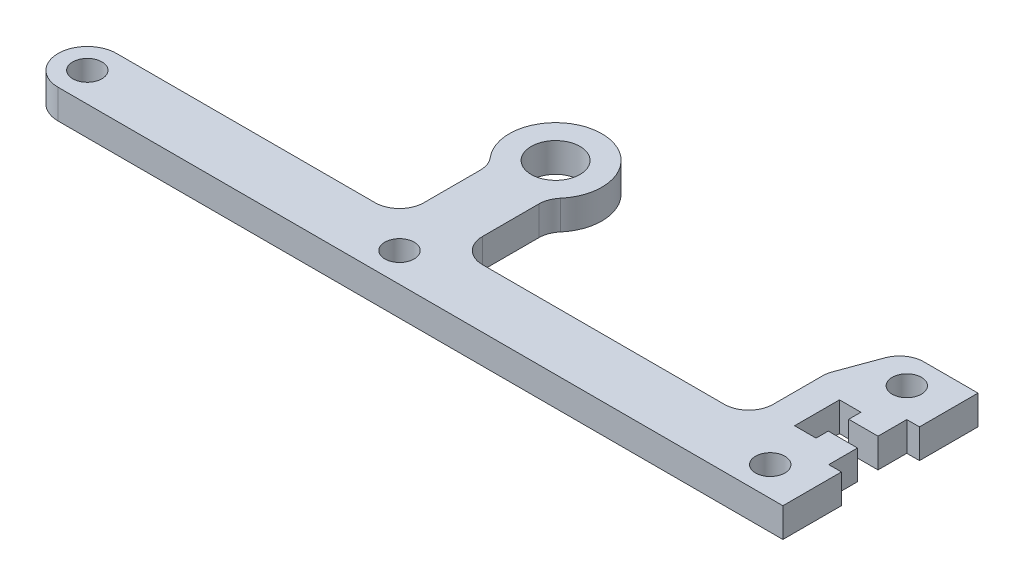
SolidWorks part; units mm, degrees
ref_plane "Front Plane" through (0, 0, 0) normal (0, 0, 1) x (1, 0, 0)
ref_plane "Top Plane" through (0, 0, 0) normal (0, 1, 0) x (1, 0, 0)
ref_plane "Right Plane" through (0, 0, 0) normal (1, 0, 0) x (0, 0, -1)
sketch "Sketch1" plane through (0, 0, 0) normal (0, 1, 0) x (1, 0, 0)
  line L0 (0, 13.2826) -> (0, -17.1967) construction
  line L5 (-2.5, 0) -> (-4.75, 0) construction
  line L6 (-3, -13) -> (3, -13)
  line L7 (-3, -13) -> (-3, -3.6827)
  line L8 (-3, -3.6827) -> (3, -3.6827)
  line L9 (3, -13) -> (3, -3.6827)
  line L10 (-3, -13) -> (3, -3.6827) construction
  line L11 (-3, -3.6827) -> (3, -13) construction
  line L12 (-19.9844, -5) -> (18.0407, -5) construction
  line L13 (-35, -19) -> (35, -19)
  line L14 (-35, -19) -> (-35, -13)
  line L15 (-35, -13) -> (35, -13)
  line L16 (35, -19) -> (35, -13)
  line L17 (-35, -19) -> (35, -13) construction
  line L18 (-35, -13) -> (35, -19) construction
  line L19 (-20.8891, -8) -> (20.8891, -8) construction
  line L20 (-35, -16) -> (35, -16) construction
  line L22 (35, -19) -> (41, -19)
  line L23 (35, -19) -> (35, 1)
  line L24 (35, 1) -> (41, 1)
  line L25 (41, -19) -> (41, 1)
  line L26 (38, 1) -> (38, -19) construction
  line L27 (35, -9) -> (41, -9) construction
  line L28 (32.8, -5) -> (32.8, -13)
  line L29 (38, -7.95) -> (41, -7.95)
  line L30 (38, -7.95) -> (38, -10.05)
  line L31 (38, -10.05) -> (41, -10.05)
  line L32 (41, -7.95) -> (41, -10.05)
  line L33 (38, -7.95) -> (41, -10.05) construction
  line L34 (38, -10.05) -> (41, -7.95) construction
  line L35 (35.8, -6.7) -> (38, -6.7)
  line L36 (35.8, -6.7) -> (35.8, -11.3)
  line L37 (35.8, -11.3) -> (38, -11.3)
  line L38 (38, -6.7) -> (38, -11.3)
  line L39 (35.8, -6.7) -> (38, -11.3) construction
  line L40 (35.8, -11.3) -> (38, -6.7) construction
  line L41 (32.8, -5) -> (35, -5)
  line L42 (32.8, -5) -> (35, 1)
  line L43 (41, -19) -> (42.3, -19)
  line L44 (41, 1) -> (42.3, 1)
  line L45 (41, 1) -> (41, -5)
  line L46 (41, -5) -> (42.3, -5)
  line L47 (42.3, 1) -> (42.3, -5)
  line L48 (42.3, -19) -> (42.3, -13)
  line L49 (41, -13) -> (42.3, -13)
  circle A2 centre (0, 0) radius 2.5
  circle A3 centre (0, 0) radius 4.75
  circle A4 centre (0, 0) radius 5
  circle A6 centre (-32, -16) radius 3
  circle A8 centre (38, -16) radius 3
  circle A9 centre (38, -2) radius 3
  circle A10 centre (-32, -16) radius 1.5
  circle A11 centre (0, -16) radius 1.5
  circle A12 centre (38, -16) radius 1.5
  circle A13 centre (38, -2) radius 1.5
  point P4 (0, -8.3414)
  point P5 (0, -16)
  point P43 (36.9, -9)
  point P45 (0, -8)
  point P46 (39.5, -9)
  point P56 (32.8, -9)
  dimension "D3" = 6
  dimension "D4" = 70
  dimension "D1" = 5
  dimension "D2" = 9.5
  dimension "D5" = 10
  dimension "D9" = 20
  dimension "D10" = 3
  dimension "D6" = 3
  dimension "D7" = 5
  dimension "D11" = 2.1
  dimension "D12" = 3
  dimension "D13" = 4.6
  dimension "D14" = 2.2
  dimension "D15" = 3
  dimension "D16" = 1.3
extrude "Boss-Extrude1" add sketch "Sketch1" along normal blind 3 contours L8 A3 A2 | L8 A3 | L7 A4 L9 A3 | A4 L7 L6 L9 | A6 L13 L16 L23 L15 L6 A11 | A6 A10 | A8 L16 L22 | A8 L22 L25 | L49 L25 L43 L48 | A8 A12 | A9 L23 A8 L25 L31 L38 L37 L36 L35 L29 | L41 L28 L15 L23 | L42 L41 L23 | L47 L44 L45 L25 L46 | A9 L45 L24 | A9 L24 L23 | A9 A13 region at (0, 0, 8.8355) region at (2.7243, 0, 16) region at (-2.9386, 0, 3.8414) region at (-29.9387, 0, 13.9387) region at (33.9, 0, 9) region at (-1.9842, 0, -4.1755) region at (0, 0, 4.114) region at (35.1523, 0, 9) region at (34.2667, 0, 3) region at (35.6701, 0, 18.3299) region at (38, 0, 13.0849) region at (35.6701, 0, -0.3299) region at (41.65, 0, 16) region at (40.3299, 0, 18.3299) region at (35.9387, 0, -0.0613) region at (40.3299, 0, -0.3299) region at (41.65, 0, 2)
fillet "Fillet1" radius 2.5 7 edges at (35, 1.5, -1) (32.8, 1.5, 5) (32.8, 1.5, 13) (3, 1.5, 13) (-3, 1.5, 13) (-3, 1.5, 3.6827) (3, 1.5, 3.6827)
